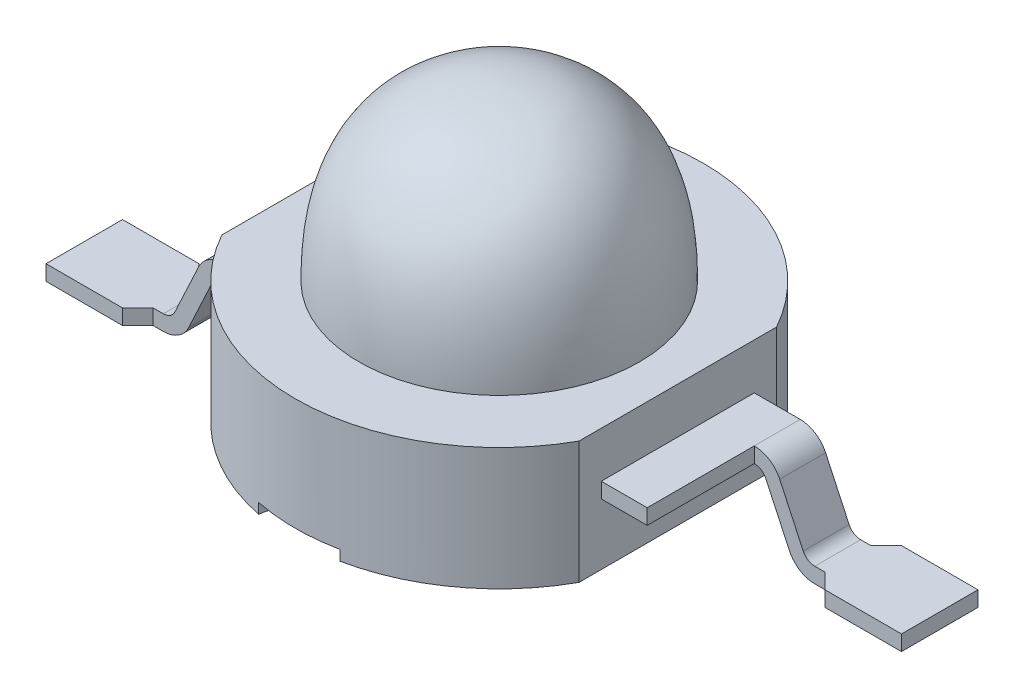
SolidWorks part; units mm, degrees
material "ABS PC"
ref_plane "Front Plane" through (0, 0, 0) normal (0, 0, 1) x (1, 0, 0)
ref_plane "Top Plane" through (0, 0, 0) normal (0, 1, 0) x (1, 0, 0)
ref_plane "Right Plane" through (0, 0, 0) normal (1, 0, 0) x (0, 0, -1)
sketch "Sketch1" plane through (0, 0, 0) normal (0, 1, 0) x (1, 0, 0)
  line L1 (-3.5, 1.9365) -> (3.5, 1.9365) construction
  line L2 (-3.5, 1.9365) -> (-3.5, -1.9365)
  line L3 (-3.5, -1.9365) -> (3.5, -1.9365) construction
  line L4 (3.5, 1.9365) -> (3.5, -1.9365)
  arc A0 (-3.5, -1.9365) -> (3.5, -1.9365) centre (0, 0) ccw
  arc A1 (3.5, 1.9365) -> (-3.5, 1.9365) centre (0, 0) ccw
  dimension "D1" = 8
  dimension "D2" = 7
extrude "Boss-Extrude1" add sketch "Sketch1" along normal blind 2.4
sketch "Sketch2" plane through (0, 0, 0) normal (0, 1, 0) x (1, 0, 0)
  circle A0 centre (0, 0) radius 2.75
  dimension "D1" = 5.5
extrude "Boss-Extrude2" add sketch "Sketch2" against normal blind 0.25
sketch "Sketch3" plane through (0, 2.4, 0) normal (0, 1, 0) x (1, 0, 0)
  circle A0 centre (0, 0) radius 2
  dimension "D1" = 4
extrude "Boss-Extrude3" add sketch "Sketch3" along normal blind 0.3
sketch "Sketch4" plane through (0, 0, 0) normal (0, 0, 1) x (1, 0, 0)
  line L0 (0, 2.4) -> (0, 5.7)
  line L1 (3.5, 2.4) -> (-3.5, 2.4) construction
  line L2 (2.75, 2.4) -> (0, 2.4)
  spline S0 degree 2 poles (2.75, 2.4) (2.7683, 4.8041) (0.7354, 5.6783) (0, 5.7) knots 0 0 0 0.79605 1 1 1
  dimension "D1" = 3.3
  dimension "D2" = 2.75
  dimension "D3" = 2
  dimension "D4" = 2.5
  dimension "D5" = 1.15
  dimension "D6" = 0.6
revolve "Revolve1" add sketch "Sketch4" angle 360 about L0
ref_plane "Plane1" through (0, 1.35, 0) normal (0, 1, 0) x (-1, 0, 0)
sketch "Sketch5" plane through (0, 1.35, 0) normal (0, 1, 0) x (-1, 0, 0)
  line L1 (-4.4, 1.5) -> (3.9, 1.5)
  line L2 (-4.4, 1.5) -> (-4.4, -1.5)
  line L3 (-4.4, -1.5) -> (3.9, -1.5)
  line L4 (3.9, 1.5) -> (3.9, -1.5)
  dimension "D1" = 8.3
  dimension "D2" = 3
  dimension "D3" = 1.5
  dimension "D4" = 4.4
extrude "Boss-Extrude4" add sketch "Sketch5" along normal mid plane 0.3
sketch "Sketch6" plane through (4.4, 0, 0) normal (1, 0, 0) x (0, 0, -1)
  line L0 (-1.5, 1.2) -> (1.5, 1.2) construction
  line L1 (1.5, 1.5) -> (0.6, 1.5)
  line L2 (1.5, 1.5) -> (1.5, 1.2)
  line L3 (1.5, 1.2) -> (0.6, 1.2)
  line L4 (0.6, 1.5) -> (0.6, 1.2)
  line L5 (1.05, 1.5) -> (1.05, 1.2) construction
  line L6 (1.05, 1.2) -> (0.6, 1.35) construction
  line L7 (0.6, 1.35) -> (1.05, 1.35) construction
  dimension "D1" = 0.9
ref_plane "Plane2" through (0, 0, -1.05) normal (0, 0, 1) x (1, 0, 0)
sketch "Sketch7" plane through (0, 0, -1.05) normal (0, 0, 1) x (1, 0, 0)
  line L0 (4.4, 1.2) -> (4.4, 1.35) construction
  line L1 (4.7625, 1.119) -> (5.2233, 0.131)
  line L2 (3.5, 1.2) -> (4.4, 1.2) construction
  line L3 (-2.75, -0.25) -> (2.75, -0.25) construction
  line L4 (5.5858, -0.1) -> (5.7858, -0.1)
  arc A0 (4.4, 1.35) -> (4.7625, 1.119) centre (4.4, 0.95) cw
  arc A1 (5.2233, 0.131) -> (5.5858, -0.1) centre (5.5858, 0.3) ccw
  point P16 (5.331, -0.1)
  dimension "D5" = 0.4
  dimension "D1" = 115
  dimension "D2" = 0.15
  dimension "D3" = 0.4
  dimension "D4" = 0.2
sweep "Sweep2" add profiles "Sketch6" path "Sketch7"
sketch "Sketch8" plane through (-3.9, 0, 0) normal (-1, 0, 0) x (0, 0, 1)
  line L0 (-1.5, 1.2) -> (1.5, 1.2) construction
  line L1 (1.5, 1.5) -> (0.6, 1.5)
  line L2 (1.5, 1.5) -> (1.5, 1.2)
  line L3 (1.5, 1.2) -> (0.6, 1.2)
  line L4 (0.6, 1.5) -> (0.6, 1.2)
  line L5 (1.05, 1.5) -> (1.05, 1.2) construction
  line L6 (1.05, 1.2) -> (0.6, 1.35) construction
  line L7 (0.6, 1.35) -> (1.05, 1.35) construction
  dimension "D1" = 0.9
ref_plane "Plane3" through (0, 0, 1.05) normal (0, 0, 1) x (1, 0, 0)
sketch "Sketch9" plane through (0, 0, 1.05) normal (0, 0, 1) x (1, 0, 0)
  line L0 (-3.9, 1.5) -> (-3.9, 1.2) construction
  line L1 (-4.2625, 1.119) -> (-4.7233, 0.131)
  line L3 (-3.5, 1.2) -> (-3.9, 1.2) construction
  line L4 (-5.0858, -0.1) -> (-5.2858, -0.1)
  line L5 (-2.75, -0.25) -> (2.75, -0.25) construction
  arc A0 (-3.9, 1.35) -> (-4.2625, 1.119) centre (-3.9, 0.95) ccw
  arc A1 (-4.7233, 0.131) -> (-5.0858, -0.1) centre (-5.0858, 0.3) cw
  dimension "D1" = 0.4
  dimension "D2" = 0.15
  dimension "D3" = 115
  dimension "D4" = 0.2
sweep "Sweep3" add profiles "Sketch8" path "Sketch9"
sketch "Sketch10" plane through (-5.2858, 0, 0) normal (-1, 0, 0) x (0, 0, 1)
  line L0 (1.5, 0.05) -> (0.6, 0.05) construction
  line L1 (0.3, 0.05) -> (1.8, 0.05)
  line L2 (0.3, 0.05) -> (0.3, -0.25)
  line L3 (0.3, -0.25) -> (1.8, -0.25)
  line L4 (1.8, 0.05) -> (1.8, -0.25)
  line L5 (0.6, -0.25) -> (1.5, -0.25) construction
  line L6 (0.6, 0.05) -> (0.6, -0.25) construction
  dimension "D1" = 1.5
  dimension "D2" = 0.3
extrude "Boss-Extrude5" add sketch "Sketch10" along normal blind 1.8
sketch "Sketch11" plane through (5.7858, 0, 0) normal (1, 0, 0) x (0, 0, -1)
  line L0 (1.5, 0.05) -> (0.6, 0.05) construction
  line L1 (0.3, 0.05) -> (1.8, 0.05)
  line L2 (0.3, 0.05) -> (0.3, -0.25)
  line L3 (0.3, -0.25) -> (1.8, -0.25)
  line L4 (1.8, 0.05) -> (1.8, -0.25)
  line L5 (0.6, -0.25) -> (1.5, -0.25) construction
  line L6 (0.6, 0.05) -> (0.6, -0.25) construction
  dimension "D1" = 1.5
  dimension "D2" = 0.3
extrude "Boss-Extrude6" add sketch "Sketch11" along normal blind 1.8
chamfer "Chamfer1" distance 0.3 angle 45 4 edges at (5.7858, -0.1, -0.3) (5.7858, -0.1, -1.8) (-5.2858, -0.1, 0.3) (-5.2858, -0.1, 1.8)
sketch "Sketch12" plane through (0, 0, 0) normal (0, -1, 0) x (1, 0, 0)
  line L0 (0, 4) -> (0, -4) construction
  line L1 (-3.5, 0) -> (3.5, 0) construction
  line L2 (-3.5, -1.9365) -> (-3.5, 1.9365) construction
  line L3 (3.5, 1.5) -> (3.5, -1.5) construction
  arc A0 (3.5, 1.9365) -> (-3.5, 1.9365) centre (0, 0) ccw construction
  arc A1 (-3.5, -1.9365) -> (3.5, -1.9365) centre (0, 0) ccw construction
  circle A2 centre (0, 4) radius 0.8
  circle A3 centre (0, -4) radius 0.8
  dimension "D1" = 1.6
extrude "Cut-Extrude1" cut sketch "Sketch12" against normal blind 0.2
